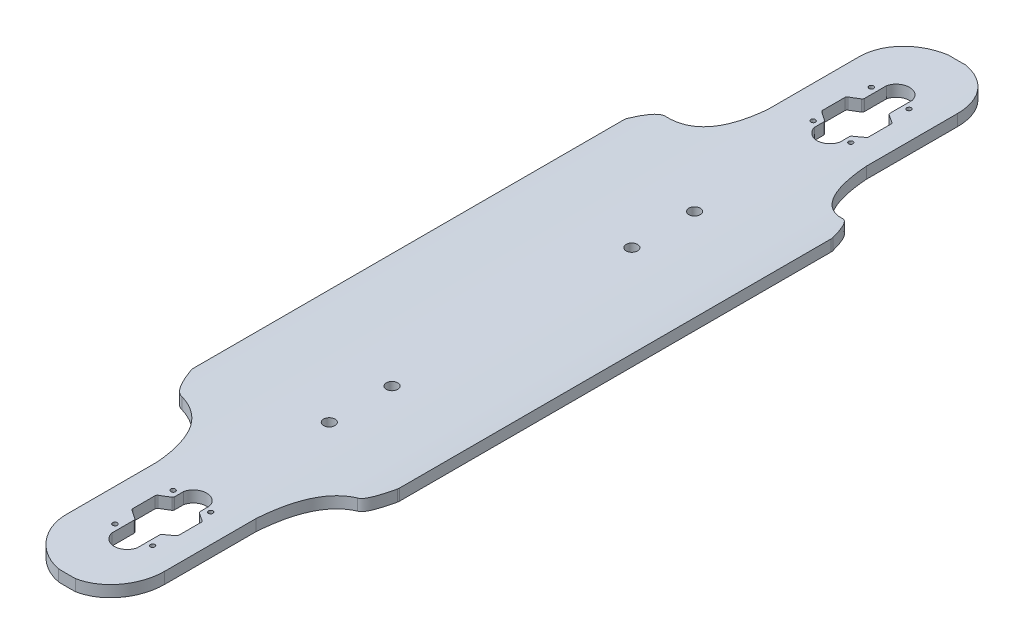
SolidWorks part; units mm, degrees
material "Maple"
ref_plane "Front Plane" through (0, 0, 0) normal (0, 0, 1) x (1, 0, 0)
ref_plane "Top Plane" through (0, 0, 0) normal (0, 1, 0) x (1, 0, 0)
ref_plane "Right Plane" through (0, 0, 0) normal (1, 0, 0) x (0, 0, -1)
sketch "Sketch1" plane through (0, 0, 0) normal (0, 0, 1) x (1, 0, 0)
  line L0 (0, 0) -> (230.1875, 0)
  line L1 (115.0937, 0) -> (115.0937, -12.7)
  line L2 (230.1875, 0) -> (230.1875, -12.7)
  line L3 (0, 0) -> (0, -12.7)
  arc A0 (230.1875, 0) -> (0, 0) centre (115.0938, 515.1686) cw
  arc A1 (230.1875, -12.7) -> (0, -12.7) centre (115.0938, 502.4686) cw
  point P6 (115.0937, -12.7)
  dimension "D1" = 2
extrude "Boss-Extrude1" add sketch "Sketch1" along normal blind 482.6 contours A1 L2 A0 L3 region at (115.0938, -14.8372, 0)
sketch "Sketch2" plane through (0, 0, 0) normal (0, 0, -1) x (-1, 0, 0)
  line L0 (-230.1875, 0) -> (-230.1875, -12.7)
  line L1 (0, 0) -> (0, -12.7)
  line L4 (-60.325, -19.05) -> (-60.325, -9.8511)
  line L5 (-169.8625, -19.05) -> (-169.8625, -9.8511)
  line L6 (-169.8625, -19.05) -> (-169.8625, -22.5511)
  line L7 (-60.325, -22.5511) -> (-60.325, -19.05)
  arc A0 (-230.1875, 0) -> (0, 0) centre (-115.0938, 515.1686) ccw
  arc A1 (-230.1875, -12.7) -> (0, -12.7) centre (-115.0938, 502.4686) ccw
  point P15 (-115.0938, -19.05)
  arc M1 (-230.1875, -12.7) -> (0, -12.7) centre (-115.0938, 502.4686) ccw
  line M2 (0, -12.7) -> (0, 0)
  arc M3 (0, 0) -> (-230.1875, 0) centre (-115.0938, 515.1686) cw
  line M4 (-230.1875, 0) -> (-230.1875, -12.7)
extrude "Boss-Extrude2" add sketch "Sketch2" along normal blind 98.425 contours L6 L5 M3 M4 M1 | L7 L4 M1 M2 M3 region at (200.025, -11.8738, 0) region at (30.1625, -11.8738, 0)
sketch "Sketch3" plane through (0, 0, 0) normal (0, 0, -1) x (-1, 0, 0)
  line L0 (-230.1875, -12.7) -> (-230.1875, 0)
  line L1 (0, 0) -> (0, -12.7)
  line L2 (-169.8625, -9.8511) -> (-169.8625, -22.5511)
  line L3 (-60.325, -9.8511) -> (-60.325, -22.5511)
  arc A0 (-230.1875, 0) -> (0, 0) centre (-115.0937, 515.1686) ccw
  arc A1 (-230.1875, -12.7) -> (0, -12.7) centre (-115.0938, 502.4686) ccw
  arc M1 (-169.8625, -22.5511) -> (-60.325, -22.5511) centre (-115.0938, 502.4686) ccw
  line M2 (-60.325, -22.5511) -> (-60.325, -9.8511)
  arc M3 (-60.325, -9.8511) -> (-169.8625, -9.8511) centre (-115.0938, 515.1686) cw
  line M4 (-169.8625, -9.8511) -> (-169.8625, -22.5511)
extrude "Boss-Extrude3" add sketch "Sketch3" along normal blind 254 contours M4 M1 M2 M3 region at (115.0938, -18.1014, 0)
sketch "Sketch4" plane through (0, 0, 482.6) normal (0, 0, 1) x (1, 0, 0)
  line L0 (0, 0) -> (0, -12.7)
  line L1 (230.1875, -12.7) -> (230.1875, 0)
  line L2 (60.325, -22.5511) -> (60.325, -9.8511)
  line L3 (169.8625, -22.5511) -> (169.8625, -9.8511)
  arc A0 (0, 0) -> (230.1875, 0) centre (115.0938, 515.1686) ccw
  arc A1 (0, -12.7) -> (230.1875, -12.7) centre (115.0938, 502.4686) ccw
  point P15 (115.0937, -19.05)
  arc M1 (0, -12.7) -> (230.1875, -12.7) centre (115.0938, 502.4686) ccw
  arc M3 (230.1875, 0) -> (0, 0) centre (115.0938, 515.1686) cw
extrude "Boss-Extrude4" add sketch "Sketch4" along normal blind 254 contours L3 L2 M1 M3 region at (115.0937, -18.1014, 482.6)
sketch "Sketch5" plane through (0, 0, 482.6) normal (0, 0, 1) x (1, 0, 0)
  line L0 (0, 0) -> (0, -12.7)
  line L1 (60.325, -9.8511) -> (60.325, -22.5511)
  line L2 (230.1875, 0) -> (230.1875, -12.7)
  line L3 (169.8625, -9.8511) -> (169.8625, -22.5511)
  arc A0 (0, 0) -> (230.1875, 0) centre (115.0938, 515.1686) ccw
  arc A1 (0, -12.7) -> (230.1875, -12.7) centre (115.0938, 502.4686) ccw
  arc M1 (0, -12.7) -> (60.325, -22.5511) centre (115.0938, 502.4686) ccw
  line M2 (60.325, -22.5511) -> (60.325, -9.8511)
  arc M3 (60.325, -9.8511) -> (0, 0) centre (115.0938, 515.1686) cw
  line M4 (0, 0) -> (0, -12.7)
extrude "Boss-Extrude5" add sketch "Sketch5" along normal blind 98.425 contours M4 M1 M2 M3 | L3 A1 L2 A0 region at (30.1625, -11.8738, 482.6) region at (200.025, -11.8738, 482.6)
ref_plane "Plane1" through (0, 0, 0) normal (0, -1, 0) x (-1, 0, 0)
sketch "Sketch6" plane through (0, 0, 0) normal (0, -1, 0) x (-1, 0, 0)
  line L0 (-115.0937, -736.6) -> (-115.0937, -482.6) construction
  line L1 (-169.8625, -736.6) -> (-60.325, -736.6) construction
  line L2 (-115.0938, 254) -> (-115.0937, 0) construction
  line L3 (-60.325, 254) -> (-169.8625, 254) construction
  line L4 (-230.1875, -482.6) -> (0, -482.6) construction
  line L5 (0, -581.025) -> (0, 98.425) construction
  line L6 (-230.1875, 0) -> (0, 0) construction
  line L7 (-60.325, -581.025) -> (0, -482.6) construction
  line L8 (-60.325, -736.6) -> (-60.325, -581.025) construction
  line L9 (-60.325, -682.625) -> (-169.8625, -682.625) construction
  line L10 (-169.8625, -736.6) -> (-169.8625, -581.025) construction
  line L11 (-169.8625, -581.025) -> (-230.1875, -482.6) construction
  line L12 (-60.325, 254) -> (-60.325, 98.425) construction
  line L13 (-60.325, 200.025) -> (-169.8625, 200.025) construction
  line L14 (-169.8625, 254) -> (-169.8625, 98.425) construction
  line L15 (-30.1625, -531.8125) -> (-200.025, -531.8125) construction
  line L16 (-230.1875, 0) -> (-169.8625, 98.425) construction
  line L17 (-60.325, 98.425) -> (0, 0) construction
  line L18 (-200.025, 49.2125) -> (-30.1625, 49.2125) construction
  line L19 (-30.1625, -531.8125) -> (-230.1875, -482.6) construction
  line L20 (-200.025, -531.8125) -> (0, -482.6) construction
  line L21 (0, 0) -> (-200.025, 49.2125) construction
  line L22 (-30.1625, 49.2125) -> (-230.1875, 0) construction
  line L23 (-230.1875, -510.9167) -> (0, -510.9167) construction
  line L24 (-230.1875, 28.3167) -> (0, 28.3167) construction
  line L25 (0, 0) -> (-8.6777, 28.3167) construction
  line L26 (-17.3554, -510.9167) -> (-8.6777, -510.9167) construction
  line L27 (-221.5098, 28.3167) -> (-230.1875, 0) construction
  line L28 (-8.6777, -510.9167) -> (0, -482.6) construction
  line L29 (-230.1875, -482.6) -> (-221.5098, -510.9167) construction
  line L30 (-212.8321, -510.9167) -> (-221.5098, -510.9167) construction
  line L31 (-8.6777, -510.9167) -> (0, -482.6) construction
  line L32 (-221.5098, -510.9167) -> (-230.1875, -482.6) construction
  line L33 (-17.3554, 28.3167) -> (-8.6777, 28.3167) construction
  line L34 (-8.6777, 28.3167) -> (0, 0) construction
  line L35 (-212.8321, 28.3167) -> (-221.5098, 28.3167) construction
  line L36 (-221.5098, 28.3167) -> (-230.1875, 0) construction
  line L38 (-60.325, -581.025) -> (0, -581.025)
  line L39 (0, -581.025) -> (0, -510.9167)
  line L40 (-60.325, -682.625) -> (-60.325, -736.6)
  line L41 (-60.325, -736.6) -> (-169.8625, -736.6)
  line L42 (-169.8625, -736.6) -> (-169.8625, -682.625)
  line L43 (-169.8625, -581.025) -> (-230.1875, -581.025)
  line L44 (-230.1875, -581.025) -> (-230.1875, -510.9167)
  line L45 (-230.1875, 0) -> (-230.1875, 98.425)
  line L46 (-230.1875, 98.425) -> (-169.8625, 98.425)
  line L47 (-169.8625, 200.025) -> (-169.8625, 254)
  line L48 (-169.8625, 254) -> (-60.325, 254)
  line L49 (-60.325, 254) -> (-60.325, 200.025)
  line L50 (-60.325, 98.425) -> (0, 98.425)
  line L51 (0, 98.425) -> (0, 0)
  line L52 (-230.1875, -482.6) -> (-230.1875, -510.9167)
  line L53 (0, -482.6) -> (0, -510.9167)
  arc A0 (-60.325, -682.625) -> (-169.8625, -682.625) centre (-115.0937, -682.625) cw
  arc A1 (-60.325, 200.025) -> (-169.8625, 200.025) centre (-115.0938, 200.025) ccw
  spline S0 degree 2 poles (-60.325, -581.025) (-55.0487, -517.0259) (-17.3554, -510.9167) knots 0 0 0 0.825721 0.825721 0.825721
  spline S1 degree 2 poles (-169.8625, -581.025) (-175.1388, -517.0259) (-212.8321, -510.9167) knots 0 0 0 0.825721 0.825721 0.825721
  spline S2 degree 2 poles (-169.8625, 98.425) (-175.1388, 34.4259) (-212.8321, 28.3167) knots 0 0 0 0.825721 0.825721 0.825721
  spline S3 degree 2 poles (-60.325, 98.425) (-55.0487, 34.4259) (-17.3554, 28.3167) knots 0 0 0 0.825721 0.825721 0.825721
  spline S4 degree 2 poles (-17.3554, -510.9167) (-8.6777, -510.9167) (0, -482.6) knots 0 0 0 1 1 1
  spline S5 degree 2 poles (-212.8321, -510.9167) (-221.5098, -510.9167) (-230.1875, -482.6) knots 0 0 0 1 1 1
  spline S6 degree 2 poles (-17.3554, 28.3167) (-8.6777, 28.3167) (0, 0) knots 0 0 0 1 1 1
  spline S7 degree 2 poles (-212.8321, 28.3167) (-221.5098, 28.3167) (-230.1875, 0) knots 0 0 0 1 1 1
  point P13 (-115.0937, -482.6)
  point P17 (-115.0937, 0)
  point P43 (-115.0938, -510.9167)
  point P44 (-17.3554, -510.9167)
  point P45 (-115.0938, 28.3167)
  point P49 (-115.0938, -510.9167)
  point P51 (-115.0938, 28.3167)
  point P53 (-212.8321, -510.9167)
  point P54 (-212.8321, 28.3167)
  point P55 (-17.3554, 28.3167)
extrude "Cut-Extrude1" cut sketch "Sketch6" along normal blind 98.425 contours L40 A0 L41 | L41 A0 L42 | S1 S5 L52 L44 L43 | S4 S0 L38 L39 L53 | S3 S6 L51 L50 | S7 S2 L46 L45 | A1 L48 L47 | A1 L49 L48 region at (25.0997, 0, 547.5668) region at (158.3996, 0, 724.4055) region at (71.7879, 0, 724.4055) region at (205.0878, 0, 547.5668) region at (205.0878, 0, -64.9668) region at (71.7879, 0, -241.8055) region at (158.3996, 0, -241.8055) region at (25.0997, 0, -64.9668)
sketch "Sketch8" plane through (0, 0, 0) normal (0, -1, 0) x (-1, 0, 0)
  line L0 (-60.325, 98.425) -> (-169.8625, 98.425) construction
  line L1 (0, 0) -> (-230.1875, 0) construction
  line L2 (-100.8698, 189.865) -> (-100.8698, 163.957)
  line L3 (-115.0938, 98.425) -> (-115.0937, 0)
  line L4 (0, -482.6) -> (-230.1875, -482.6)
  line L5 (0, -241.3) -> (-230.1875, -241.3)
  line L6 (0, -482.6) -> (0, 0) construction
  line L7 (-230.1875, -482.6) -> (-230.1875, 0) construction
  line L8 (-100.8698, 163.957) -> (-89.4398, 156.337)
  line L9 (-89.4398, 156.337) -> (-89.4398, 128.905)
  line L10 (-89.4398, 128.905) -> (-100.8698, 121.285)
  line L11 (-100.8698, 121.285) -> (-100.8698, 109.855)
  line L12 (-129.3177, 109.855) -> (-129.3177, 121.285)
  line L13 (-129.3177, 121.285) -> (-140.7477, 128.905)
  line L14 (-140.7477, 128.905) -> (-140.7477, 156.337)
  line L15 (-140.7477, 156.337) -> (-129.3177, 163.957)
  line L16 (-129.3177, 163.957) -> (-129.3177, 189.865)
  line L17 (-115.0938, 98.425) -> (-115.0938, 114.935) construction
  line L18 (-115.0938, 201.295) -> (-115.0938, 179.705) construction
  line L19 (-94.1388, 179.705) -> (-136.0488, 179.705) construction
  line L20 (-94.1388, 114.935) -> (-136.0488, 114.935) construction
  line L21 (-94.1387, -597.535) -> (-136.0487, -597.535) construction
  line L22 (-94.1387, -662.305) -> (-136.0487, -662.305) construction
  line L23 (-115.0937, -683.895) -> (-115.0937, -662.305) construction
  line L24 (-115.0937, -581.025) -> (-115.0937, -597.535) construction
  line L25 (-129.3177, -646.557) -> (-129.3177, -672.465)
  line L26 (-140.7477, -638.937) -> (-129.3177, -646.557)
  line L27 (-140.7477, -611.505) -> (-140.7477, -638.937)
  line L28 (-129.3177, -603.885) -> (-140.7477, -611.505)
  line L29 (-129.3177, -592.455) -> (-129.3177, -603.885)
  line L30 (-100.8698, -603.885) -> (-100.8698, -592.455)
  line L31 (-89.4398, -611.505) -> (-100.8698, -603.885)
  line L32 (-89.4398, -638.937) -> (-89.4398, -611.505)
  line L33 (-100.8698, -646.557) -> (-89.4398, -638.937)
  line L34 (-100.8698, -672.465) -> (-100.8698, -646.557)
  arc A0 (-100.8698, 189.865) -> (-129.3177, 189.865) centre (-115.0938, 186.7295) ccw
  arc A1 (-100.8698, 109.855) -> (-129.3177, 109.855) centre (-115.0938, 112.9905) cw
  circle A2 centre (-136.0488, 179.705) radius 2.54
  circle A3 centre (-136.0488, 114.935) radius 2.54
  circle A4 centre (-94.1388, 114.935) radius 2.54
  circle A5 centre (-94.1388, 179.705) radius 2.54
  circle A6 centre (-94.1387, -597.535) radius 2.54
  circle A7 centre (-136.0487, -597.535) radius 2.54
  circle A8 centre (-136.0487, -662.305) radius 2.54
  arc A9 (-100.8698, -592.455) -> (-129.3177, -592.455) centre (-115.0937, -595.5905) ccw
  arc A10 (-100.8698, -672.465) -> (-129.3177, -672.465) centre (-115.0937, -669.3295) cw
  circle A11 centre (-94.1387, -662.305) radius 2.54
  point P26 (-115.0937, 189.865)
  point P29 (-115.0938, 201.295)
  point P30 (-115.0938, 98.425)
  point P42 (-115.0938, 179.705)
  point P46 (-115.0938, 114.935)
  point P47 (-100.8698, 163.957)
  point P48 (-89.4398, 156.337)
  point P49 (-89.4398, 128.905)
  point P50 (-100.8698, 121.285)
  point P51 (-100.8698, 109.855)
  point P52 (-129.3177, 109.855)
  point P53 (-129.3177, 121.285)
  point P54 (-140.7477, 128.905)
  point P55 (-140.7477, 156.337)
  point P56 (-129.3177, 163.957)
  point P57 (-129.3177, 189.865)
  point P58 (-100.8698, 189.865)
  point P59 (-100.8698, 163.957)
  point P60 (-89.4398, 156.337)
  point P87 (-115.0937, -672.465)
extrude "Cut-Extrude2" cut sketch "Sketch8" along normal blind 30.48 contours A1 L11 L10 L9 L8 L2 A0 L16 L15 L14 L13 L12 | A4 | A10 L34 L33 L32 L31 L30 A9 L29 L28 L27 L26 L25 | A2 | A5 | A3 | A11 | A8 | A6 | A7 region at (115.0937, 0, -148.2319) region at (115.0937, 0, 630.8319) region at (94.1388, 0, -114.935)
fillet "Fillet2" radius 2.54 16 edges at (100.8698, -18.8583, -121.285) (89.4398, -18.4262, -128.905) (89.4398, -18.4262, -156.337) (100.8698, -18.8583, -163.957) (129.3177, -18.8583, -121.285) (140.7477, -18.4262, -128.905) (140.7477, -18.4262, -156.337) (129.3177, -18.8583, -163.957) (140.7477, -18.4262, 638.937) (140.7477, -18.4262, 611.505) (89.4398, -18.4262, 638.937) (89.4398, -18.4262, 611.505) (129.3177, -18.8583, 646.557) (129.3177, -18.8583, 603.885) (100.8698, -18.8583, 646.557) (100.8698, -18.8583, 603.885)
fillet "Fillet1" radius 7.62 4 edges at (0, -6.35, 0) (0, -6.35, 482.6) (230.1875, -6.35, 0) (230.1875, -6.35, 482.6)
sketch "Sketch9" plane through (0, 0, 0) normal (0, -1, 0) x (-1, 0, 0)
  line L0 (-115.0937, -736.6) -> (-115.0938, -88.7823) construction
  line L1 (-124.3844, -736.6) -> (-105.8031, -736.6) construction
  line L2 (-105.8031, 254) -> (-124.3844, 254) construction
  line L3 (0, -481.4477) -> (-230.1875, -481.4477) construction
  line L4 (-230.1875, -1.1523) -> (0, -1.1523) construction
  line L5 (-115.0937, -481.4477) -> (-115.0938, -470.0177) construction
  line L6 (-115.0938, -470.0177) -> (-115.0938, -400.1677) construction
  line L7 (0, -241.3) -> (-230.1875, -241.3) construction
  line L8 (0, -481.4477) -> (0, -1.1523) construction
  line L9 (-230.1875, -481.4477) -> (-230.1875, -1.1523) construction
  line L10 (-115.0938, -76.0823) -> (-115.0938, 254) construction
  circle A4 centre (-115.0938, -444.6177) radius 6.35
  circle A5 centre (-115.0938, -374.7677) radius 6.35
  circle A6 centre (-115.0938, -107.8323) radius 6.35
  circle A7 centre (-115.0938, -37.9823) radius 6.35
  point P23 (-115.0937, -82.4323)
  point P24 (-115.0937, -12.5823)
extrude "Cut-Extrude3" cut sketch "Sketch9" along normal blind 38.1
